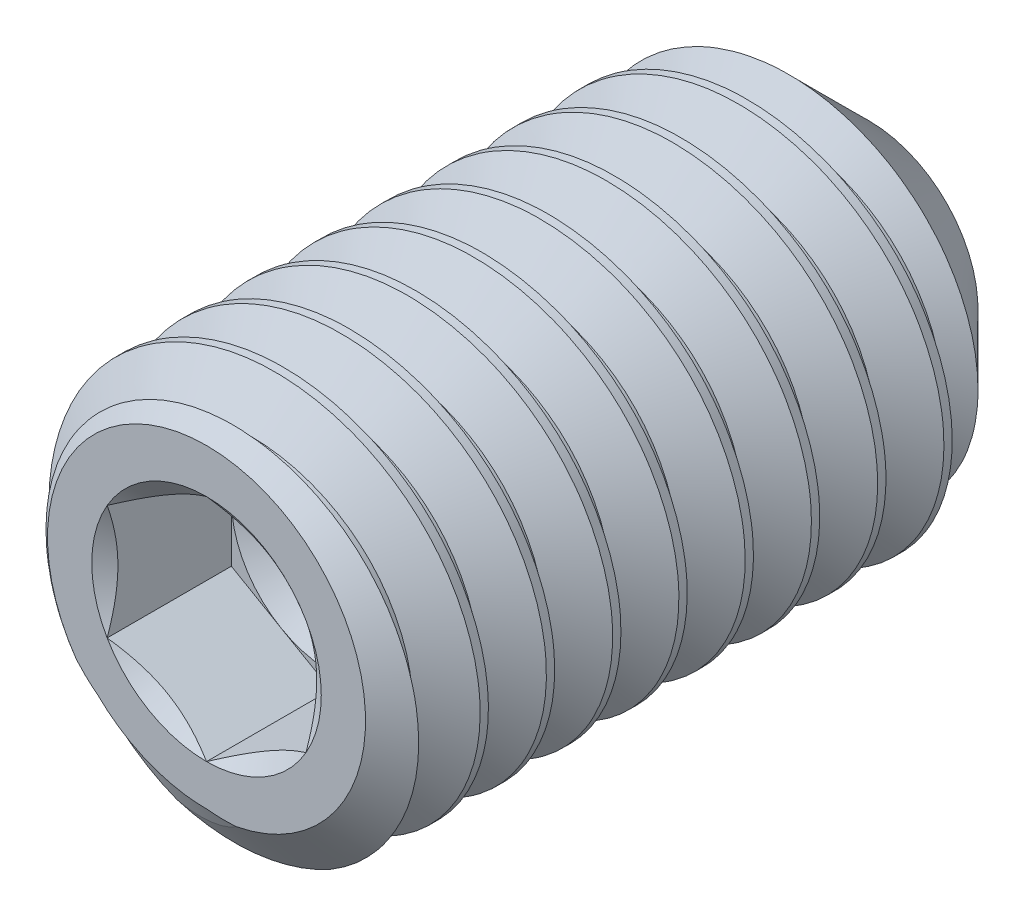
SolidWorks part; units mm, degrees
ref_plane "Front" through (0, 0, 0) normal (0, 0, 1) x (1, 0, 0)
ref_plane "Top" through (0, 0, 0) normal (0, 1, 0) x (1, 0, 0)
ref_plane "Right" through (0, 0, 0) normal (1, 0, 0) x (0, 0, -1)
sketch "Body Sketch" plane through (0, 0, 0) normal (1, 0, 0) x (0, 0, -1)
  line L0 (-2.2531, 0) -> (-2.2531, 1.2)
  line L1 (-2.2531, 1.2) -> (-2.043, 1.5)
  line L2 (-2.043, 1.5) -> (2.0689, 1.5)
  line L3 (2.0689, 1.5) -> (2.7469, 0.8219)
  line L4 (0.0129, 1.5) -> (0.0129, -1.5) construction
  line L5 (2.2531, 0) -> (-2.2531, 0)
  line L6 (-2.2531, 1.2) -> (-2.2531, -1.2) construction
  line L7 (2.2531, 0) -> (2.7469, 0.8219)
  line L8 (2.2531, 0) -> (2.7469, -0.8219) construction
  line L10 (2.2531, 0) -> (2.7469, 0) construction
  line L11 (2.7469, 0.8219) -> (2.7469, 0) construction
  point P11 (0.0129, 0)
  dimension "Length" = 5
  dimension "Top Chamfer" = 35
  dimension "Diameter" = 3
  dimension "D1" = 2.4
  dimension "D2" = 118
  dimension "D3" = 45
revolve "Body Revolve" add sketch "Body Sketch" angle 360 about L5
ref_plane "Bottom of Tip Plane" through (0, 0, -2.7469) normal (0, 0, 1) x (1, 0, 0)
sketch "Spiral Sketch" plane through (0, 0, -2.7469) normal (0, 0, 1) x (1, 0, 0)
  circle A0 centre (0, 0) radius 1.5 construction
  circle A1 centre (0, 0) radius 1.5
curve "Helix/Spiral" pitch 0.5 height 5.5 radius 1.5 centre (0, 0, -2.7469) axis (0, 0, 1) start towards (0, 1, 0) parameters "Thread Pitch"=0.5
sketch "Cut Sweep Sketch" plane through (0, 0, 0) normal (1, 0, 0) x (0, 0, -1)
  line L0 (2.7469, 1.5) -> (3.1844, 1.5)
  line L1 (3.1844, 1.5) -> (2.9969, 1.1752)
  line L2 (2.9969, 1.1752) -> (2.9344, 1.1752)
  line L3 (2.9344, 1.1752) -> (2.7469, 1.5)
  line L4 (2.8407, 1.3376) -> (3.0907, 1.3376) construction
  line L6 (-2.043, 1.5) -> (2.0689, 1.5) construction
  dimension "D1" = 0.0625
  dimension "D3" = 60
  dimension "D2" = 0.25
sweep "Cut Sweep" cut profiles "Cut Sweep Sketch" path "Helix/Spiral" align with end faces yes
sketch "Hex Sketch" plane through (0, 0, 2.2531) normal (0, 0, 1) x (1, 0, 0)
  line L1 (0, 0.866) -> (-0.75, 0.433)
  line L2 (-0.75, 0.433) -> (-0.75, -0.433)
  line L3 (-0.75, -0.433) -> (0, -0.866)
  line L4 (0, -0.866) -> (0.75, -0.433)
  line L5 (0.75, -0.433) -> (0.75, 0.433)
  line L6 (0.75, 0.433) -> (0, 0.866)
  circle A0 centre (0, 0) radius 0.75 construction
  dimension "Hex" = 1.5
extrude "Hex Extrude" cut sketch "Hex Sketch" against normal blind 0.9375
sketch "Hex Entry Sketch" plane through (0, 0, 2.2531) normal (0, 0, 1) x (1, 0, 0)
  circle A0 centre (0, 0) radius 0.866
extrude "Hex Entry Extrude" cut sketch "Hex Entry Sketch" against normal through all draft 55
sketch "Hex Bottom Sketch" plane through (0, 0, 1.3156) normal (0, 0, 1) x (1, 0, 0)
  circle A0 centre (0, 0) radius 0.75 construction
  circle A1 centre (0, 0) radius 0.75
extrude "Hex Bottom Extrude" cut sketch "Hex Bottom Sketch" against normal through all draft 60
ref_axis "Centerline Axis" through (0, 0, -2.2531) along (0, 0, 1)
equation "\"D1@Cut Sweep Sketch\" = \"Thread Pitch@Helix/Spiral\" * .125"
equation "\"D2@Cut Sweep Sketch\" = \"Thread Pitch@Helix/Spiral\" * .5"
equation "\"D3@Helix/Spiral\" = \"Length@Body Sketch\" + \"Thread Pitch@Helix/Spiral\""
equation "\"hex Depth@Hex Extrude\" = \"Hex@Hex Sketch\" * .625"
equation "\"D1@Body Sketch\" = \"Diameter@Body Sketch\" * .8"
equation "\"Diameter\"= 3mm"
equation "\"Thread Pitch\"= 0.5mm"
equation "\"Hex Size\"= 1.5mm"
equation "\"Diameter@Body Sketch\"=\"Diameter\""
equation "\"Thread Pitch@Helix/Spiral\"=\"Thread Pitch\""
equation "\"Hex@Hex Sketch\"=\"Hex Size\""
